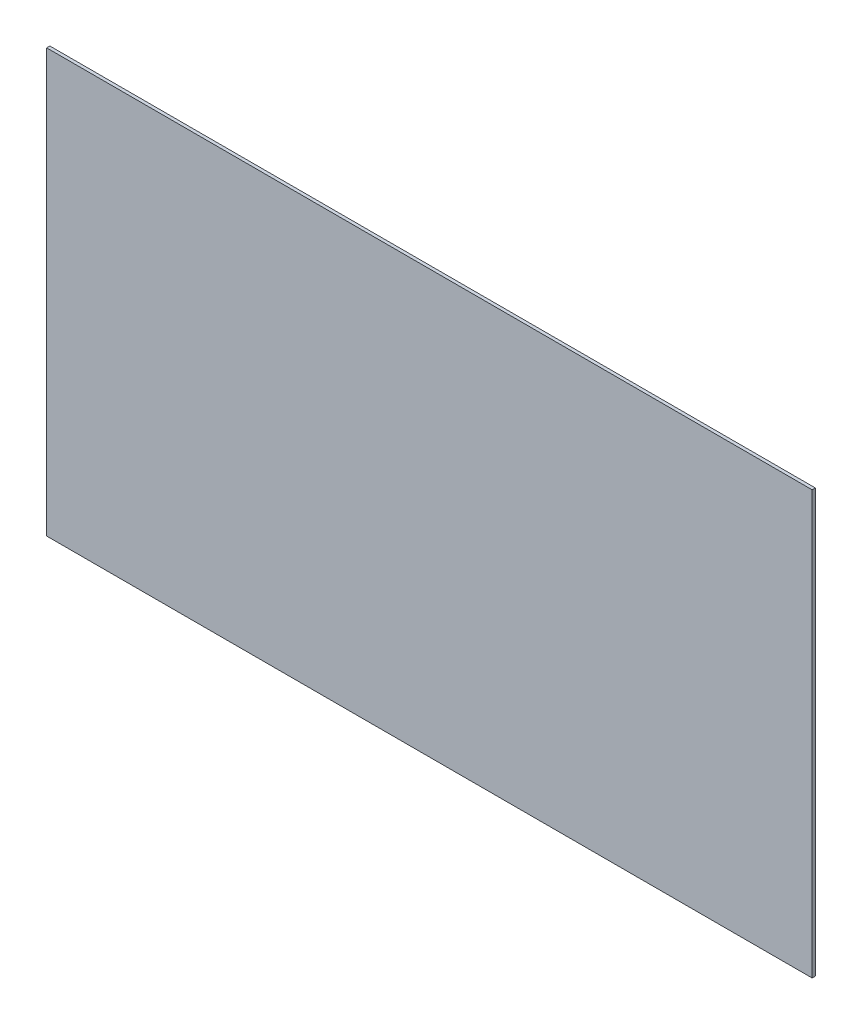
SolidWorks part; units mm, degrees
ref_plane "Front Plane" through (0, 0, 0) normal (0, 0, 1) x (1, 0, 0)
ref_plane "Top Plane" through (0, 0, 0) normal (0, 1, 0) x (1, 0, 0)
ref_plane "Right Plane" through (0, 0, 0) normal (1, 0, 0) x (0, 0, -1)
sketch "Sketch1" plane through (0, 0, 0) normal (0, 0, 1) x (1, 0, 0)
  line L1 (-27.051, 6.35) -> (-785.749, 6.35)
  line L2 (-27.051, 6.35) -> (-27.051, 425.45)
  line L3 (-27.051, 425.45) -> (-785.749, 425.45)
  line L4 (-785.749, 6.35) -> (-785.749, 425.45)
extrude "Boss-Extrude1" add sketch "Sketch1" along normal blind 3.175 contours L3 L4 L1 L2
